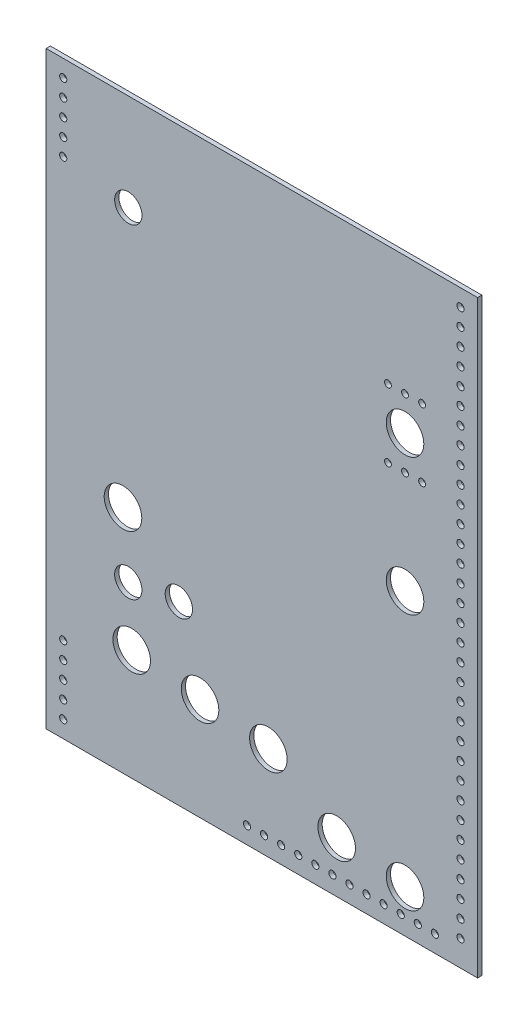
SolidWorks part; units mm, degrees
ref_plane "Front Plane" through (0, 0, 0) normal (0, 0, 1) x (1, 0, 0)
ref_plane "Top Plane" through (0, 0, 0) normal (0, 1, 0) x (1, 0, 0)
ref_plane "Right Plane" through (0, 0, 0) normal (1, 0, 0) x (0, 0, -1)
sketch "Sketch1" plane through (0, 0, 0) normal (0, 0, 1) x (1, 0, 0)
  line L1 (-160.401, 219.075) -> (160.401, 219.075)
  line L2 (-160.401, 219.075) -> (-160.401, -219.075)
  line L3 (-160.401, -219.075) -> (160.401, -219.075)
  line L4 (160.401, 219.075) -> (160.401, -219.075)
  line L5 (-160.401, 219.075) -> (160.401, -219.075) construction
  line L6 (-160.401, -219.075) -> (160.401, 219.075) construction
  point P0 (0, 0)
  dimension "D1" = 438.15
  dimension "D2" = 320.802
extrude "Boss-Extrude1" add sketch "Sketch1" along normal blind 3.175
sketch "Sketch2" plane through (0, 0, 3.175) normal (0, 0, 1) x (1, 0, 0)
  line L0 (160.401, -219.075) -> (106.4458, -219.075) construction
  line L1 (-160.401, -219.075) -> (160.401, -219.075) construction
  line L2 (106.4458, -219.075) -> (106.4458, -187.325) construction
  line L3 (106.4458, -219.075) -> (55.626, -219.075) construction
  line L4 (55.626, -219.075) -> (55.626, -180.975) construction
  line L5 (55.626, -219.075) -> (4.826, -219.075) construction
  line L6 (4.826, -219.075) -> (4.826, -149.225) construction
  line L7 (4.826, -219.075) -> (-45.974, -219.075) construction
  line L8 (-45.974, -219.075) -> (-45.974, -142.875) construction
  line L9 (-45.974, -219.075) -> (-96.774, -219.075) construction
  line L10 (-96.774, -219.075) -> (-96.774, -136.525) construction
  line L11 (106.4458, -187.325) -> (106.4458, 3.175) construction
  circle A0 centre (106.4458, -187.325) radius 13.97
  circle A1 centre (55.626, -180.975) radius 13.97
  circle A2 centre (4.826, -149.225) radius 13.97
  circle A3 centre (-45.974, -142.875) radius 13.97
  circle A4 centre (-96.774, -136.525) radius 13.97
  circle A5 centre (106.4458, 3.175) radius 13.97
  circle A6 centre (106.4458, 104.775) radius 13.97
  circle A7 centre (93.7458, 130.175) radius 2.54
  circle A8 centre (106.4458, 130.175) radius 2.54
  circle A9 centre (119.1458, 130.175) radius 2.54
  circle A10 centre (93.7458, 79.375) radius 2.54
  circle A11 centre (106.4458, 79.375) radius 2.54
  circle A12 centre (119.1458, 79.375) radius 2.54
  dimension "D1" = 69.85
  dimension "D6" = 190.5
  dimension "D7" = 50.8
  dimension "D11" = 27.94
  dimension "D12" = 5.08
  dimension "D2" = 76.2
  dimension "D3" = 82.55
  dimension "D4" = 38.1
  dimension "D5" = 31.75
  dimension "D8" = 25.4
  dimension "D9" = 12.7
  dimension "D10" = 12.7
  dimension "D13" = 101.6
extrude "Cut-Extrude1" cut sketch "Sketch2" against normal blind 3.175
sketch "Sketch3" plane through (0, 0, 3.175) normal (0, 0, 1) x (1, 0, 0)
  line L0 (-160.401, -219.075) -> (-99.314, -219.075) construction
  line L1 (-160.401, -219.075) -> (160.401, -219.075) construction
  line L2 (-99.314, -219.075) -> (-99.314, -94.107) construction
  line L3 (-160.401, -219.075) -> (-61.722, -219.075) construction
  line L4 (-61.722, -219.075) -> (-61.722, -87.757) construction
  line L5 (-99.314, -94.107) -> (-61.722, -87.757) construction
  circle A0 centre (-99.314, -94.107) radius 10.16
  circle A1 centre (-61.722, -87.757) radius 10.16
  circle A2 centre (-99.314, 147.193) radius 10.16
  dimension "D2" = 241.3
  dimension "D1" = 124.968
  dimension "D3" = 170.412
extrude "Cut-Extrude3" cut sketch "Sketch3" against normal blind 3.175 contours A2 | A1 | A0 region at (-99.314, 147.193, 3.175)
sketch "Sketch4" plane through (0, 0, 3.175) normal (0, 0, 1) x (1, 0, 0)
  line L0 (-160.401, -219.075) -> (-160.401, -206.4814) construction
  line L1 (-160.401, 219.075) -> (-160.401, -219.075) construction
  line L2 (-160.401, -206.4814) -> (-147.701, -206.4814) construction
  line L3 (-160.401, 0) -> (160.401, 0) construction
  line L4 (160.401, -219.075) -> (160.401, 219.075) construction
  line L5 (0, -219.075) -> (0, 219.075) construction
  line L6 (-160.401, -219.075) -> (160.401, -219.075) construction
  line L7 (160.401, 219.075) -> (-160.401, 219.075) construction
  circle A0 centre (-147.701, -206.4814) radius 2.667
  circle A14 centre (-147.701, -193.7814) radius 2.667
  circle A15 centre (-147.701, -181.0814) radius 2.667
  circle A16 centre (-147.701, -168.3814) radius 2.667
  circle A17 centre (-147.701, -155.6814) radius 2.667
  circle A18 centre (-147.701, 206.4814) radius 2.667
  circle A19 centre (-147.701, 193.7814) radius 2.667
  circle A20 centre (-147.701, 181.0814) radius 2.667
  circle A21 centre (-147.701, 168.3814) radius 2.667
  circle A22 centre (-147.701, 155.6814) radius 2.667
  circle A28 centre (147.701, 155.6814) radius 2.667
  circle A29 centre (147.701, 168.3814) radius 2.667
  circle A30 centre (147.701, 181.0814) radius 2.667
  circle A31 centre (147.701, 193.7814) radius 2.667
  circle A32 centre (147.701, 206.4814) radius 2.667
  circle A61 centre (147.701, 142.9814) radius 2.667
  circle A62 centre (147.701, 130.2814) radius 2.667
  circle A63 centre (147.701, 117.5814) radius 2.667
  circle A64 centre (147.701, 104.8814) radius 2.667
  circle A65 centre (147.701, 92.1814) radius 2.667
  circle A66 centre (147.701, 79.4814) radius 2.667
  circle A67 centre (147.701, 66.7814) radius 2.667
  circle A68 centre (147.701, 54.0814) radius 2.667
  circle A69 centre (147.701, 41.3814) radius 2.667
  circle A70 centre (147.701, 28.6814) radius 2.667
  circle A71 centre (147.701, 15.9814) radius 2.667
  circle A72 centre (147.701, 3.2814) radius 2.667
  circle A73 centre (147.701, -9.4186) radius 2.667
  circle A74 centre (147.701, -22.1186) radius 2.667
  circle A75 centre (147.701, -34.8186) radius 2.667
  circle A76 centre (147.701, -47.5186) radius 2.667
  circle A77 centre (147.701, -60.2186) radius 2.667
  circle A78 centre (147.701, -72.9186) radius 2.667
  circle A79 centre (147.701, -85.6186) radius 2.667
  circle A80 centre (147.701, -98.3186) radius 2.667
  circle A81 centre (147.701, -111.0186) radius 2.667
  circle A82 centre (147.701, -123.7186) radius 2.667
  circle A83 centre (147.701, -136.4186) radius 2.667
  circle A84 centre (147.701, -149.1186) radius 2.667
  circle A85 centre (147.701, -161.8186) radius 2.667
  circle A86 centre (147.701, -174.5186) radius 2.667
  circle A87 centre (147.701, -187.2186) radius 2.667
  circle A88 centre (147.701, -199.9186) radius 2.667
  circle A89 centre (103.251, -206.4814) radius 2.667
  circle A90 centre (115.951, -206.4814) radius 2.667
  circle A91 centre (128.651, -206.4814) radius 2.667
  circle A92 centre (90.551, -206.4814) radius 2.667
  circle A93 centre (65.151, -206.4814) radius 2.667
  circle A94 centre (77.851, -206.4814) radius 2.667
  circle A95 centre (52.451, -206.4814) radius 2.667
  circle A96 centre (39.751, -206.4814) radius 2.667
  circle A97 centre (27.051, -206.4814) radius 2.667
  circle A98 centre (14.351, -206.4814) radius 2.667
  circle A99 centre (1.651, -206.4814) radius 2.667
  circle A100 centre (-11.049, -206.4814) radius 2.667
  dimension "D3" = 12.7
  dimension "D5" = 29
  dimension "D2" = 5
extrude "Cut-Extrude4" cut sketch "Sketch4" against normal blind 3.175
sketch "Sketch5" plane through (0, 0, 3.175) normal (0, 0, 1) x (1, 0, 0)
  line L0 (-160.401, 219.075) -> (-160.401, -219.075) construction
  line L1 (-160.401, -219.075) -> (160.401, -219.075) construction
  circle A0 centre (-103.251, -47.8361) radius 13.97
  dimension "D1" = 57.15
  dimension "D2" = 171.2389
extrude "Cut-Extrude5" cut sketch "Sketch5" against normal blind 3.175
equation "\"D2@Sketch5\"=6.25+.365+0.1266891891"
